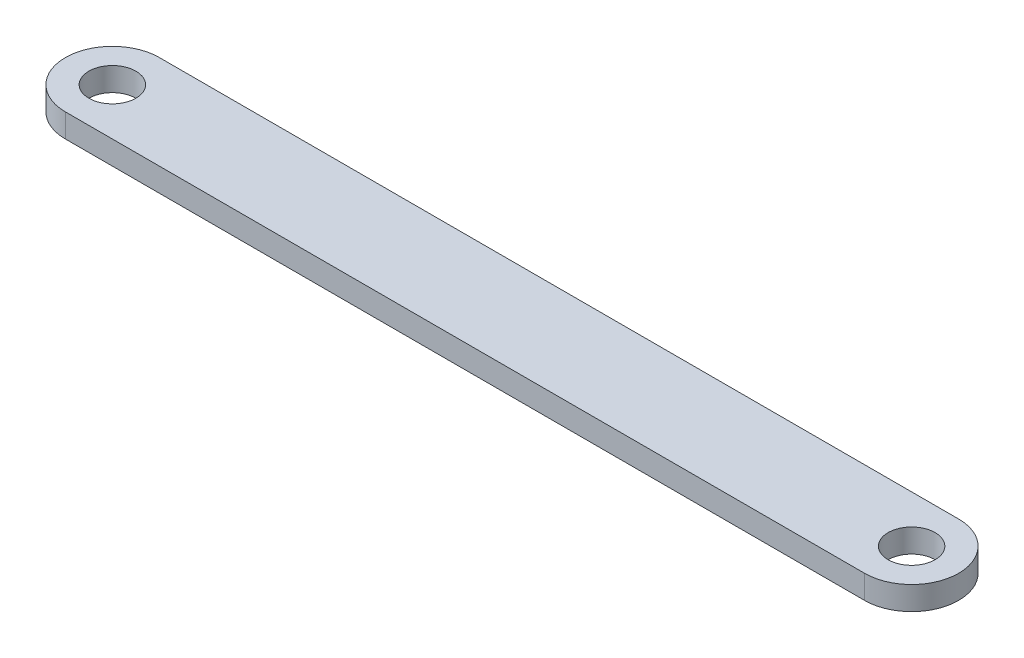
SolidWorks part; units mm, degrees
ref_plane "Ön Düzlem" through (0, 0, 0) normal (0, 0, 1) x (1, 0, 0)
ref_plane "Üst Düzlem" through (0, 0, 0) normal (0, 1, 0) x (1, 0, 0)
ref_plane "Sağ Düzlem" through (0, 0, 0) normal (1, 0, 0) x (0, 0, -1)
sketch "Sketch1" plane through (0, 0, 0) normal (0, 1, 0) x (1, 0, 0)
  line L0 (-85, 0) -> (85, 0) construction
  line L1 (-85, 10) -> (85, 10)
  line L2 (-85, -10) -> (85, -10)
  arc A0 (-85, 10) -> (-85, -10) centre (-85, 0) ccw
  arc A1 (85, -10) -> (85, 10) centre (85, 0) ccw
  circle A2 centre (-85, 0) radius 5
  circle A3 centre (85, 0) radius 5
  point P2 (0, 0)
  dimension "D1" = 10
  dimension "D3" = 10
  dimension "D4" = 10
  dimension "D2" = 170
extrude "Boss-Extrude1" add sketch "Sketch1" along normal blind 5
